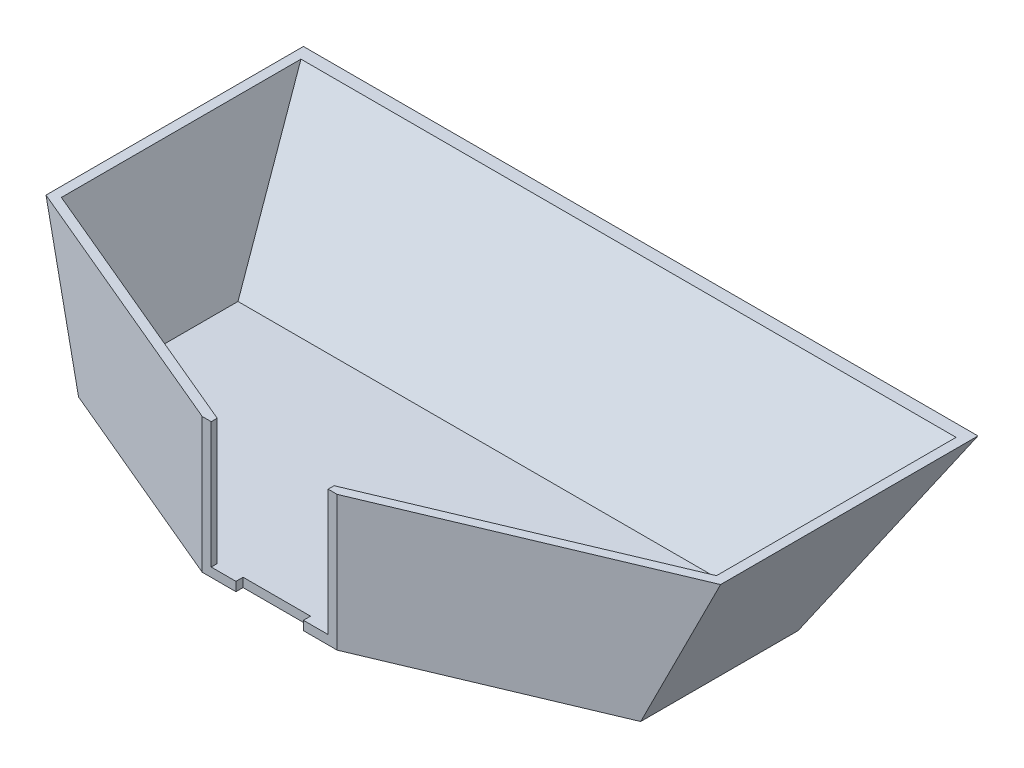
SolidWorks part; units mm, degrees
ref_plane "Front Plane" through (0, 0, 0) normal (0, 0, 1) x (1, 0, 0)
ref_plane "Top Plane" through (0, 0, 0) normal (0, 1, 0) x (1, 0, 0)
ref_plane "Right Plane" through (0, 0, 0) normal (1, 0, 0) x (0, 0, -1)
sketch "Sketch1" plane through (0, 0, 0) normal (0, 1, 0) x (1, 0, 0)
  line L0 (0, 0) -> (0, -68.0967) construction
  line L2 (125, -35) -> (125, 35)
  line L3 (125, 35) -> (-125, 35)
  line L4 (-125, -35) -> (-125, 35)
  line L5 (125, -35) -> (-125, 35) construction
  line L6 (125, 35) -> (-125, -35) construction
  line L7 (125, -35) -> (30, -75)
  line L8 (-125, -35) -> (-30, -75)
  line L9 (-30, -75) -> (30, -75)
  point P0 (0, 0)
  dimension "D1" = 250
  dimension "D2" = 70
  dimension "D3" = 30
ref_plane "Plane1" through (0, 60, 0) normal (0, 1, 0) x (1, 0, 0)
sketch "Sketch2" plane through (0, 60, 0) normal (0, 1, 0) x (1, 0, 0)
  line L0 (0, 0) -> (0, 61.1496) construction
  line L2 (-150, -24.4737) -> (-150, 90)
  line L3 (-150, 90) -> (150, 90)
  line L4 (150, -24.4737) -> (150, 90)
  line L5 (125, 35) -> (-125, -35) construction
  line L10 (-30, -75) -> (-150, -24.4737)
  line L11 (-125, -35) -> (-30, -75) construction
  line L12 (30, -75) -> (150, -24.4737)
  line L13 (-30, -75) -> (30, -75)
  dimension "D1" = 300
loft "Loft2" add profiles "Sketch2", "Sketch1" connector at (-150, 60, 24.4737) connector at (-125, 0, 35)
shell "Shell2" thickness 4 removed face at (-15, 45, 75) removed face at (0, 60, 3.1579)
sketch "Sketch5" plane through (0, 0, 75) normal (0, 0, 1) x (1, 0, 0)
  line L1 (-26, 4) -> (-15, 4)
  line L2 (-26, 4) -> (-26, 60)
  line L3 (-26, 60) -> (26, 60)
  line L4 (26, 4) -> (26, 60)
  line L5 (90.7501, 60) -> (-90.7501, 60) construction
  line L6 (-30, 60) -> (-30, 0) construction
  line L7 (30, 60) -> (30, 0) construction
  line L9 (-30, 0) -> (30, 0) construction
  line L10 (-15, 0) -> (-15, 4)
  line L11 (0, 0) -> (0, 32.3358) construction
  line L12 (15, 0) -> (15, 4)
  line L13 (15, 4) -> (26, 4)
  line L14 (-15, 0) -> (15, 0)
  dimension "D1" = 4
  dimension "D2" = 4
  dimension "D3" = 4
  dimension "D4" = 15
extrude "Cut-Extrude1" cut sketch "Sketch5" against normal blind 3.175
